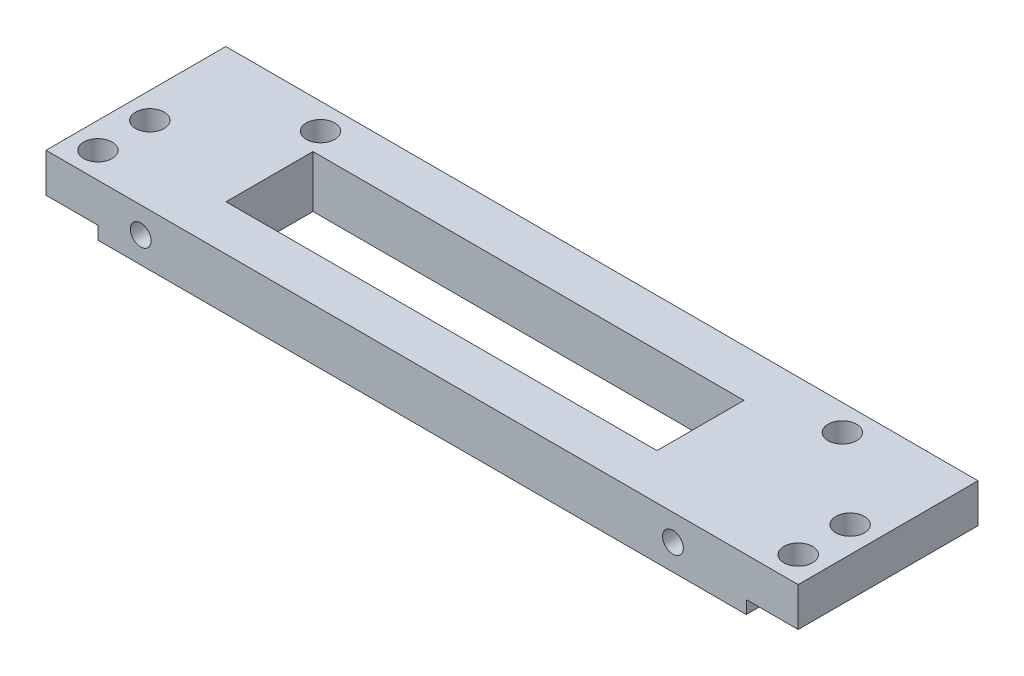
SolidWorks part; units mm, degrees
material "6061-T6 (SS)"
ref_plane "前视基准面" through (0, 0, 0) normal (0, 0, 1) x (1, 0, 0)
ref_plane "上视基准面" through (0, 0, 0) normal (0, 1, 0) x (1, 0, 0)
ref_plane "右视基准面" through (0, 0, 0) normal (1, 0, 0) x (0, 0, -1)
other "Configuration Table"
sketch "草图1" plane through (0, 0, 0) normal (0, 0, 1) x (1, 0, 0)
  line L1 (-4.3, 41.68) -> (53.65, 41.68)
  line L2 (-4.3, 41.68) -> (-4.3, 45.68)
  line L3 (-4.3, 45.68) -> (53.65, 45.68)
  line L4 (53.65, 41.68) -> (53.65, 45.68)
  dimension "D1" = 53.65
  dimension "D2" = 4.3
  dimension "D3" = 41.68
  dimension "D4" = 45.68
extrude "Main_Stock" add sketch "草图1" along normal blind 8.8519 from offset 2.2481
sketch "草图2" plane through (0, 0, 11.1) normal (0, 0, 1) x (1, 0, 0)
  line L1 (-4.3, 41.68) -> (-0.3, 41.68)
  line L2 (-4.3, 41.68) -> (-4.3, 42.68)
  line L3 (-4.3, 42.68) -> (-0.3, 42.68)
  line L4 (-0.3, 41.68) -> (-0.3, 42.68)
  dimension "D1" = 0.3
  dimension "D2" = 4.3
  dimension "D3" = 41.68
  dimension "D4" = 42.68
extrude "Corner_Left_Rectangular_Notch_4x1" cut sketch "草图2" against normal blind 8.8519
sketch "草图3" plane through (0, 0, 11.1) normal (0, 0, 1) x (1, 0, 0)
  line L1 (49.65, 41.68) -> (53.65, 41.68)
  line L2 (49.65, 41.68) -> (49.65, 42.68)
  line L3 (49.65, 42.68) -> (53.65, 42.68)
  line L4 (53.65, 41.68) -> (53.65, 42.68)
  dimension "D1" = 49.65
  dimension "D2" = 53.65
  dimension "D3" = 41.68
  dimension "D4" = 42.68
extrude "Corner_Right_Rectangular_Notch_4x1" cut sketch "草图3" against normal blind 8.8519
sketch "草图4" plane through (0, 0, 11.1) normal (0, 0, 1) x (1, 0, 0)
  circle A0 centre (3, 43.68) radius 0.8
  circle A1 centre (44, 43.68) radius 0.8
  dimension "D1" = 1.6
  dimension "D2" = 3
  dimension "D3" = 44
  dimension "D4" = 43.68
extrude "Frame_2xD1p6_Through" cut sketch "草图4" against normal through all
cosmetic thread "Frame_M2_Through_Cosmetic_1" parameters "D2"=2
cosmetic thread "Frame_M2_Through_Cosmetic_2" parameters "D2"=2
sketch "草图5" plane through (0, 45.68, 0) normal (0, 1, 0) x (1, 0, 0)
  line L1 (6.07, -0.9) -> (39.273, -0.9)
  line L2 (6.07, -0.9) -> (6.07, -7.6)
  line L3 (6.07, -7.6) -> (39.273, -7.6)
  line L4 (39.273, -0.9) -> (39.273, -7.6)
  dimension "D1" = 6.07
  dimension "D2" = 39.273
  dimension "D3" = 0.9
  dimension "D4" = 7.6
extrude "Merged_Interface_Window_33p203x6p7" cut sketch "草图5" against normal blind 4
sketch "草图6" plane through (0, 45.68, 0) normal (0, 1, 0) x (1, 0, 0)
  circle A0 centre (-2.3, -5.1) radius 1.1
  circle A1 centre (-2.3, -9.1) radius 1.1
  circle A2 centre (51.65, -5.1) radius 1.1
  circle A3 centre (51.65, -9.1) radius 1.1
  dimension "D1" = 2.2
  dimension "D2" = 51.65
  dimension "D3" = 2.3
  dimension "D4" = 5.1
  dimension "D5" = 9.1
extrude "Corner_Rear_4xD2p2_Through" cut sketch "草图6" against normal through all
sketch "草图7" plane through (0, 0, 2.2481) normal (0, 0, -1) x (-1, 0, 0)
  line L0 (4.3, 42.68) -> (0.3, 42.68)
  line L1 (0.3, 42.68) -> (0.3, 41.68)
  line L2 (0.3, 41.68) -> (-49.65, 41.68)
  line L3 (-49.65, 41.68) -> (-49.65, 42.68)
  line L4 (-49.65, 42.68) -> (-53.65, 42.68)
  line L5 (-53.65, 42.68) -> (-53.65, 45.68)
  line L6 (-53.65, 45.68) -> (4.3, 45.68)
  line L7 (4.3, 45.68) -> (4.3, 42.68)
  dimension "D1" = 0.3
  dimension "D2" = 4.3
  dimension "D3" = 49.65
  dimension "D4" = 41.68
  dimension "D5" = 42.68
  dimension "D6" = 45.68
extrude "Wall_Extension_To_Floor" add sketch "草图7" along normal blind 5
sketch "草图8" plane through (0, 45.68, 0) normal (0, 1, 0) x (1, 0, 0)
  line L1 (6.07, -0.9) -> (39.273, -0.9)
  line L2 (6.07, -0.9) -> (6.07, -7.6)
  line L3 (6.07, -7.6) -> (39.273, -7.6)
  line L4 (39.273, -0.9) -> (39.273, -7.6)
  dimension "D1" = 6.07
  dimension "D2" = 39.273
  dimension "D3" = 0.9
  dimension "D4" = 7.6
extrude "Rear_Window_Full_33p203x6p7" cut sketch "草图8" against normal blind 4.01
sketch "草图9" plane through (0, 45.68, 0) normal (0, 1, 0) x (1, 0, 0)
  circle A0 centre (5, 0.75) radius 1.1
  circle A1 centre (45.2, 0.75) radius 1.1
  dimension "D1" = 2.2
  dimension "D2" = 5
  dimension "D3" = 45.2
  dimension "D4" = 0.75
extrude "Horizontal_Base_M2_1_0.04568" cut sketch "草图9" against normal blind 4.01
